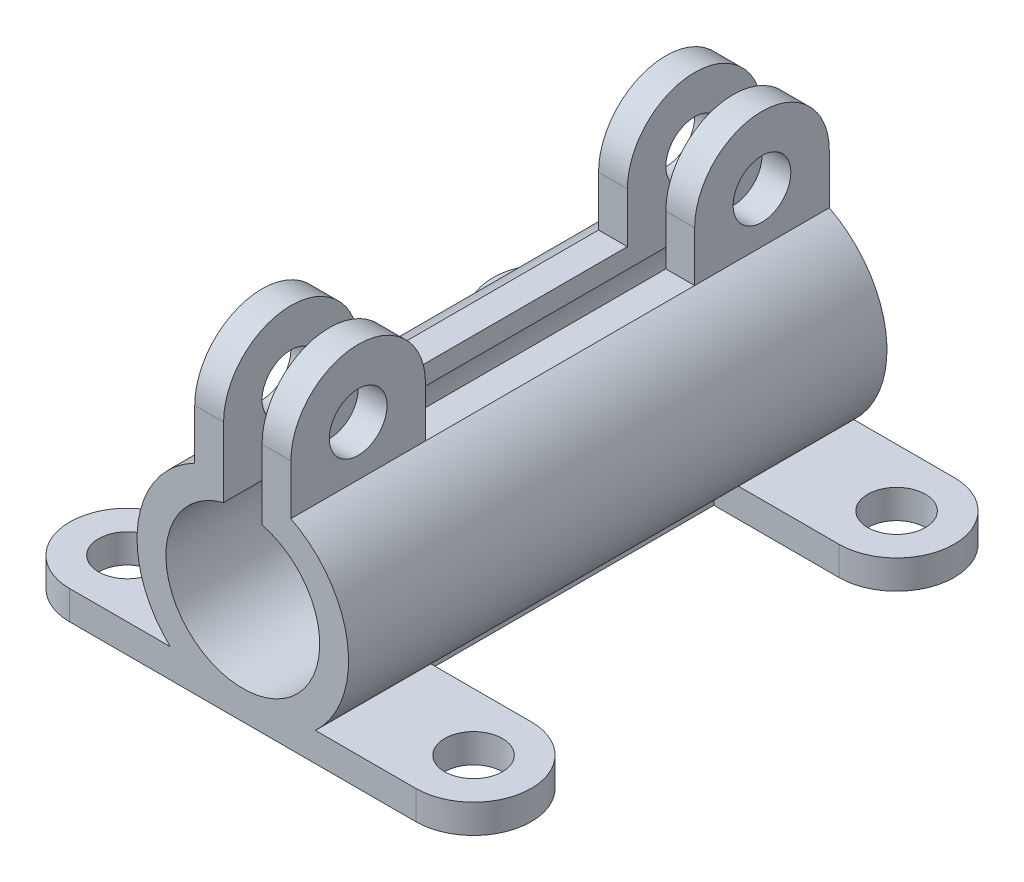
SolidWorks part; units mm, degrees
ref_plane "Front Plane" through (0, 0, 0) normal (0, 0, 1) x (1, 0, 0)
ref_plane "Top Plane" through (0, 0, 0) normal (0, 1, 0) x (1, 0, 0)
ref_plane "Right Plane" through (0, 0, 0) normal (1, 0, 0) x (0, 0, -1)
sketch "Sketch1" plane through (0, 0, 0) normal (0, 0, 1) x (1, 0, 0)
  line L0 (-120, -40) -> (-37.7492, -40)
  line L1 (-120, -55) -> (120, -55)
  line L2 (37.7492, -40) -> (120, -40)
  line L3 (-120, -40) -> (-120, -55)
  line L4 (-120, -40) -> (120, -40) construction
  line L5 (120, -40) -> (120, -55)
  line L6 (25, 48.9898) -> (25, 110)
  line L8 (10, 38.7298) -> (10, 110)
  line L9 (-25, 110) -> (-10, 110)
  line L11 (10, 110) -> (25, 110)
  line L12 (-120, 110) -> (120, 110) construction
  line L13 (-25, 48.9898) -> (-25, 110)
  line L14 (-10, 38.7298) -> (-10, 110)
  arc A0 (-10, 38.7298) -> (10, 38.7298) centre (0, 0) ccw
  arc A1 (37.7492, -40) -> (25, 48.9898) centre (0, 0) ccw
  arc A2 (-25, 48.9898) -> (-37.7492, -40) centre (0, 0) ccw
  point P3 (306.2685, 145.2676)
  point P11 (587.9777, -223.2599)
  point P12 (587.9777, -118.1359)
  point P13 (587.9777, -145.728)
  point P19 (280.4454, -118.1359)
  point P23 (280.4454, -133.3809)
  point P24 (587.9777, -118.1359)
  point P25 (587.9777, -145.728)
  point P26 (587.9777, -223.2599)
  dimension "D1" = 80
  dimension "D2" = 55
  dimension "D4" = 240
  dimension "D5" = 120
  dimension "D6" = 165
  dimension "D7" = 10
  dimension "D8" = 25
  dimension "D3" = 15
extrude "Boss-Extrude1" add sketch "Sketch1" against normal blind 280
sketch "Sketch5" plane through (0, -40, 0) normal (0, 1, 0) x (1, 0, 0)
  line L1 (120, 220) -> (120, 60)
  line L3 (-120, 60) -> (-120, 220)
  line L4 (-120, 220) -> (-24.219, 220)
  line L5 (120, 60) -> (25, 60)
  line L6 (-37.7492, 280) -> (-37.7492, 0) construction
  line L8 (-24.219, 220) -> (-24.219, 60)
  line L9 (25, 220) -> (25, 60)
  line L10 (25, 220) -> (120, 220)
  line L11 (-37.7492, 0) -> (-120, 0) construction
  line L13 (-24.219, 60) -> (-120, 60)
  line L14 (-120, 280) -> (-120, 0) construction
  point P5 (-25, 280)
  point P6 (-25, 0)
  point P7 (25, 280)
  point P8 (25, 0)
  dimension "D1" = 13.5301
  dimension "D2" = 62.7492
  dimension "D3" = 157.7492
  dimension "D4" = 0
  dimension "D5" = 60
  dimension "D6" = 220
  dimension "D7" = 280
extrude "Cut-Extrude9" cut sketch "Sketch5" against normal blind 280 contours L5 L9 L10 L1 | L13 L3 L4 L8
fillet "Fillet1" 2 edges at (-120, -47.5, -280) (-120, -47.5, -220) type full round first side face at (0, 19.5228, -280) second side face at (-65.2375, -46, -220) middle face at (-120, -47.5, -250)
fillet "Fillet2" 2 edges at (-120, -47.5, -60) (-120, -47.5, 0) type full round first side face at (-65.2375, -46, -60) second side face at (0, 19.5228, 0) middle face at (-120, -47.5, -30)
fillet "Fillet3" 2 edges at (120, -47.5, -280) (120, -47.5, -220) type full round first side face at (4.2857, 19.5228, -280) second side face at (65.5498, -46, -220) middle face at (120, -47.5, -250)
fillet "Fillet4" 2 edges at (120, -47.5, -60) (120, -47.5, 0) type full round first side face at (65.5498, -46, -60) second side face at (4.2857, 19.5228, 0) middle face at (120, -47.5, -30)
sketch "Sketch7" plane through (0, -40, 0) normal (0, 1, 0) x (1, 0, 0)
  circle A0 centre (-90, 250) radius 15
  circle A1 centre (90, 250) radius 15
  circle A2 centre (90, 30) radius 15
  circle A3 centre (-90, 30) radius 15
  dimension "D1" = 30
  dimension "D2" = 30
  dimension "D3" = 30
  dimension "D4" = 30
extrude "Cut-Extrude10" cut sketch "Sketch7" against normal blind 280
sketch "Sketch8" plane through (25, 0, 0) normal (1, 0, 0) x (0, 0, -1)
  line L0 (70, 110) -> (210, 110)
  line L2 (210, 48.9898) -> (70, 48.9898)
  line L5 (280, 48.9898) -> (0, 48.9898) construction
  line L6 (70, 110) -> (70, 48.9898)
  line L7 (210, 110) -> (210, 48.9898)
  line L8 (0, 48.9898) -> (0, 110) construction
  dimension "D1" = 70
  dimension "D2" = 210
  dimension "D3" = 280
  dimension "D4" = 61.0102
extrude "Cut-Extrude11" cut sketch "Sketch8" against normal blind 280
fillet "Fillet5" 2 edges at (17.5, 110, 0) (17.5, 110, -70) type full round first side face at (0, 19.5228, 0) second side face at (17.5, 79.4949, -70) middle face at (17.5, 110, -35)
fillet "Fillet6" 2 edges at (-17.5, 110, 0) (-17.5, 110, -70) type full round first side face at (0, 14.5228, 0) second side face at (-17.5, 79.4949, -70) middle face at (-17.5, 110, -35)
fillet "Fillet7" 2 edges at (-17.5, 110, -210) (-17.5, 110, -280) type full round first side face at (-17.5, 79.4949, -210) second side face at (0, 19.5228, -280) middle face at (-17.5, 110, -245)
fillet "Fillet8" 2 edges at (17.5, 110, -280) (17.5, 110, -210) type full round first side face at (0, 14.5228, -280) second side face at (17.5, 79.4949, -210) middle face at (17.5, 110, -245)
sketch "Sketch9" plane through (25, 0, 0) normal (1, 0, 0) x (0, 0, -1)
  circle A0 centre (35, 75) radius 15
  circle A1 centre (245, 75) radius 15
  dimension "D1" = 30
  dimension "D2" = 30
extrude "Cut-Extrude12" cut sketch "Sketch9" against normal blind 280
